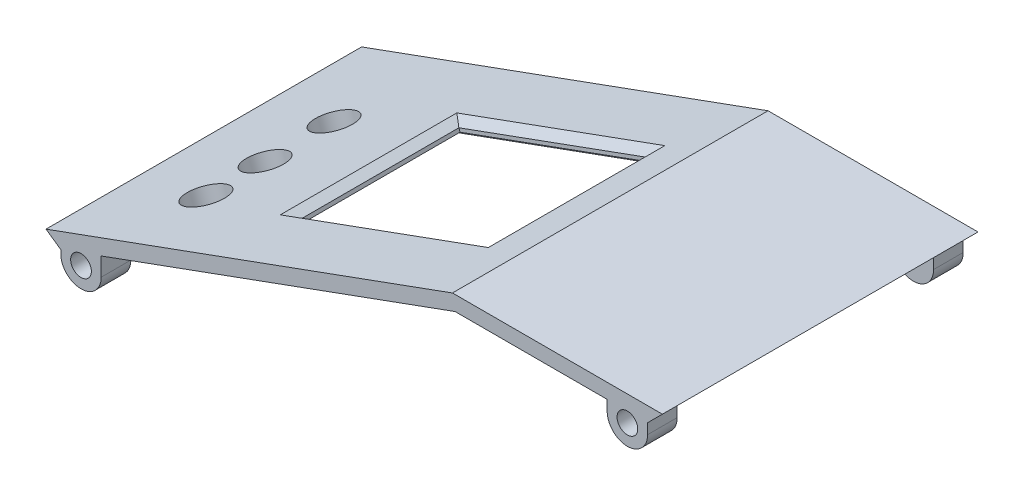
SolidWorks part; units mm, degrees
ref_plane "Спереди" through (0, 0, 0) normal (0, 0, 1) x (1, 0, 0)
ref_plane "Сверху" through (0, 0, 0) normal (0, 1, 0) x (1, 0, 0)
ref_plane "Справа" through (0, 0, 0) normal (1, 0, 0) x (0, 0, -1)
sketch "Эскиз1" plane through (0, 0, 0) normal (0, 0, 1) x (1, 0, 0)
  line L1 (62.5, 80) -> (19.9243, 80)
  line L2 (19.9243, 80) -> (-62.5, 50)
  line L5 (-59.5, 47.8994) -> (20.4533, 77)
  line L6 (20.4533, 77) -> (59.5, 77)
  line L7 (59.5, 77) -> (62.5, 80)
  line L8 (62.5, 80) -> (59.5, 77) construction
  line L9 (-59.5, 47.8994) -> (-62.5, 50)
  line L13 (-62.5, 50) -> (-62.5, 0) construction
  point P0 (59.5, 77)
  dimension "D1" = 3
  dimension "D2" = 20
extrude "Бобышка-Вытянуть1" add sketch "Эскиз1" along normal mid plane 64
sketch "Эскиз2" plane through (0, 0, 0) normal (0, 0, 1) x (1, 0, 0)
  line L2 (51.3, 80) -> (51.3, 74.9)
  line L4 (59.5, 77) -> (59.5, 9.2) construction
  line L5 (59.5, 74.9) -> (59.5, 80)
  line L6 (62.5, 80) -> (19.9243, 80) construction
  line L7 (59.5, 80) -> (51.3, 80)
  line L9 (-51.3, 54.0765) -> (-51.3, 47.1569)
  line L10 (19.9243, 80) -> (-62.5, 50) construction
  line L11 (-59.5, 3) -> (-59.5, 47.8994) construction
  line L12 (-59.5, 47.1569) -> (-59.5, 51.0919)
  line L13 (-59.5, 51.0919) -> (-51.3, 54.0765)
  arc A0 (51.3, 74.9) -> (59.5, 74.9) centre (55.4, 74.9) ccw
  circle A1 centre (55.4, 74.9) radius 2.1
  arc A2 (-51.3, 47.1569) -> (-59.5, 47.1569) centre (-55.4, 47.1569) cw
  circle A3 centre (-55.4, 47.1569) radius 2.1
  dimension "D1" = 4.2
  dimension "D2" = 2
  dimension "D3" = 3
  dimension "D4" = 2
  dimension "D5" = 3
extrude "Бобышка-Вытянуть2" add sketch "Эскиз2" against normal blind 6 from surface contours L2 A0 L5 L7 A1 | A1 | A2 L9 L13 L12 A3 | A3 region at (55.4, 79.8768, 0) region at (-51.4374, 50.6167, 0) region at (55.4, 74.9, 0) region at (-55.4, 47.1569, 0) starting at face at (6.7296, 68.6499, 32)
extrude "Бобышка-Вытянуть3" add sketch "Эскиз2<3>" along normal blind 6 from surface contours A1 | L2 A0 L5 L7 A1 | A2 L9 L13 L12 A3 | A3 region at (55.4, 79.8768, 0) region at (-51.4374, 50.6167, 0) region at (55.4, 74.9, 0) region at (-55.4, 47.1569, 0) starting at face at (6.7296, 68.6499, -32)
sketch "Эскиз2<3>" plane through (0, 0, 0) normal (0, 0, 1) x (1, 0, 0) same geometry as "Эскиз2"
extrude "Вырез-Вытянуть1" cut sketch "Эскиз2<4>" against normal blind 4 from surface contours A1 | A3 region at (55.4, 74.9, 0) region at (-55.4, 47.1569, 0) starting at face at (3.3648, 64.6414, 32)
sketch "Эскиз2<4>" plane through (0, 0, 0) normal (0, 0, 1) x (1, 0, 0) same geometry as "Эскиз2"
extrude "Вырез-Вытянуть2" cut sketch "Эскиз2<5>" along normal blind 4 from surface contours A1 | A3 region at (55.4, 74.9, 0) region at (-55.4, 47.1569, 0) starting at face at (3.3648, 64.6414, -32)
sketch "Эскиз2<5>" plane through (0, 0, 0) normal (0, 0, 1) x (1, 0, 0) same geometry as "Эскиз2"
sketch "Эскиз3" plane through (-22.3547, 61.4191, 0) normal (0.342, -0.9397, 0) x (0.9397, 0.342, 0)
  line L8 (-9.7792, -17.5) -> (-9.7792, -14.8)
  line L9 (38.4208, -17.5) -> (-9.7792, -17.5)
  line L10 (38.4208, 17.5) -> (38.4208, -17.5)
  line L11 (-9.5792, 17.5) -> (38.4208, 17.5)
  line L12 (-9.7792, -17.5) -> (-9.7792, 17.5)
  line L13 (38.4208, -17.5) -> (-9.7792, -17.5)
  line L14 (38.4208, 17.5) -> (38.4208, -17.5)
  line L15 (-9.7792, 17.5) -> (38.4208, 17.5)
  dimension "D1" = 0.2
extrude "Вырез-Вытянуть3" cut sketch "Эскиз3" against normal blind 0.8
sketch "Эскиз4" plane through (-22.3547, 61.4191, 0) normal (0.342, -0.9397, 0) x (0.9397, 0.342, 0)
  line L16 (-4.5792, -16.4) -> (37.3208, -16.4)
  line L17 (-4.5792, 16.4) -> (-4.5792, -16.4)
  line L18 (37.3208, 16.4) -> (-4.5792, 16.4)
  line L19 (37.3208, -16.4) -> (37.3208, 16.4)
  line L20 (-4.5792, -16.4) -> (37.3208, -16.4)
  line L21 (-4.5792, 16.4) -> (-4.5792, -16.4)
  line L22 (37.3208, 16.4) -> (-4.5792, 16.4)
  line L23 (37.3208, -16.4) -> (37.3208, 16.4)
  dimension "D1" = 0.5
extrude "Вырез-Вытянуть4" cut sketch "Эскиз4" against normal through all
sketch "Эскиз7" plane through (-23.3808, 64.2382, 0) normal (-0.342, 0.9397, 0) x (0.9397, 0.342, 0)
  circle A2 centre (-24.4292, 10.25) radius 4
  circle A3 centre (-24.4292, 10.25) radius 4
  circle A20 centre (-24.4142, -3.75) radius 4
  circle A21 centre (-24.4142, -15.75) radius 4
  dimension "D2" = 8
  dimension "D1" = 0.5
extrude "Вырез-Вытянуть5" cut sketch "Эскиз7" against normal blind 10
sketch "Эскиз8" plane through (-22.3547, 61.4191, 0) normal (0.342, -0.9397, 0) x (0.9397, 0.342, 0)
  line L0 (38.4208, -17.5) -> (38.4208, 17.5) construction
  circle A1 centre (40.9708, 15) radius 2.55
  circle A4 centre (40.9708, -15) radius 2.55
  circle A7 centre (-36.0292, -16.5) radius 2.55
  circle A8 centre (-36.0292, 16.5) radius 2.55
extrude "Бобышка-Вытянуть4" add sketch "Эскиз8" along normal up to surface (2 mm away)
sketch "Эскиз9" plane through (-21.6707, 59.5398, 0) normal (0.342, -0.9397, 0) x (0.9397, 0.342, 0)
  circle A0 centre (40.9708, -15) radius 1.4
  circle A1 centre (40.9708, 15) radius 1.4
  circle A2 centre (-36.0292, -16.5) radius 1.4
  circle A3 centre (-36.0292, 16.5) radius 1.4
  dimension "D1" = 2.8
extrude "Вырез-Вытянуть6" cut sketch "Эскиз9" against normal blind 3
chamfer "Фаска1" distance 1.5 angle 45 4 edges at (11.6893, 77.0027, 0) (-7.9972, 69.8374, -16.4) (-27.6838, 62.6721, 0) (-7.9972, 69.8374, 16.4)
